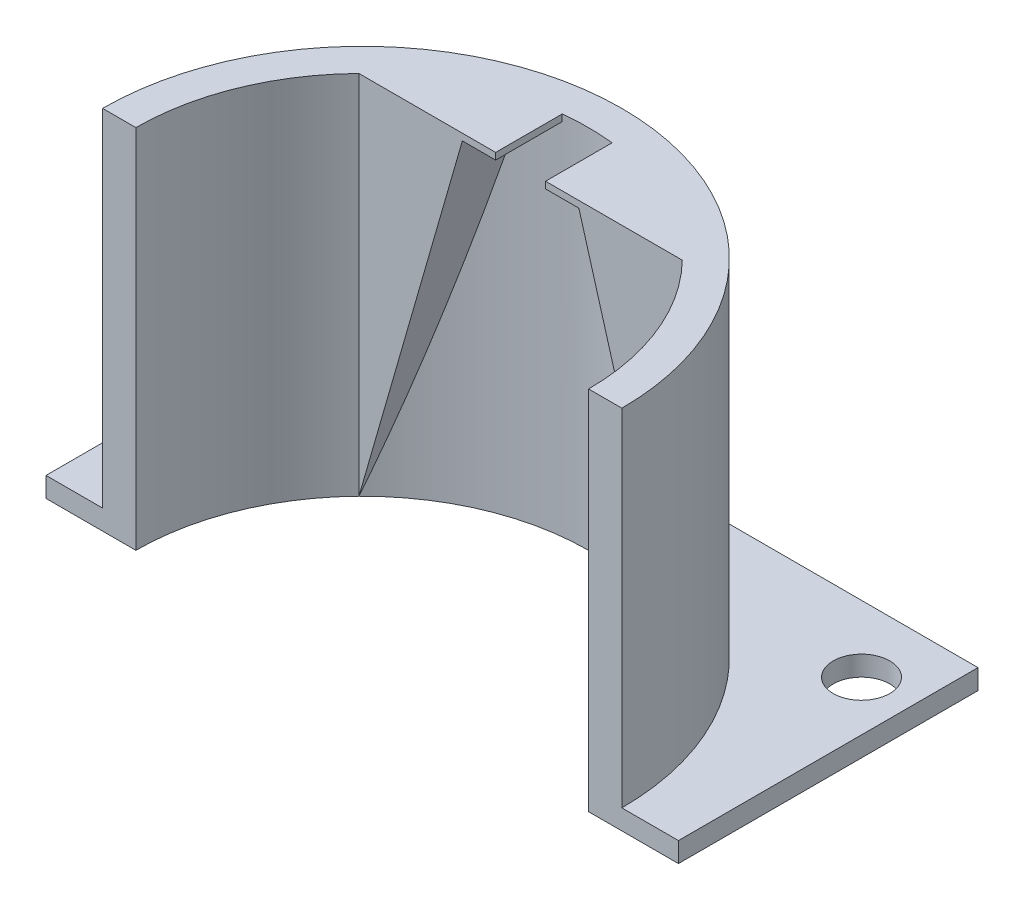
SolidWorks part; units mm, degrees
ref_plane "Front Plane" through (0, 0, 0) normal (0, 0, 1) x (1, 0, 0)
ref_plane "Top Plane" through (0, 0, 0) normal (0, 1, 0) x (1, 0, 0)
ref_plane "Right Plane" through (0, 0, 0) normal (1, 0, 0) x (0, 0, -1)
sketch "Sketch1" plane through (0, 0, 0) normal (0, 1, 0) x (1, 0, 0)
  line L0 (-47.5, 0) -> (47.5, 0)
  line L2 (-55, 0) -> (55, 0) construction
  line L3 (0, 0) -> (0, -45) construction
  line L4 (0, -55) -> (0, 55) construction
  line L5 (-47.5, 0) -> (-47.5, -45)
  line L7 (47.5, -45) -> (47.5, 0)
  line L8 (-47.5, -45) -> (-34, -45)
  line L9 (34, -45) -> (47.5, -45)
  arc A0 (34, -45) -> (-34, -45) centre (0, -45) ccw
  point P4 (0, 0)
  point P17 (0, -11)
  dimension "D3" = 68
  dimension "D4" = 34
  dimension "D1" = 95
  dimension "D2" = 45
extrude "Boss-Extrude1" add sketch "Sketch1" along normal blind 55
sketch "Sketch2" plane through (0, 55, 0) normal (0, 1, 0) x (1, 0, 0)
  line L0 (-47.5, -45) -> (-34, -45) construction
  line L1 (34, -45) -> (47.5, -45) construction
  line L2 (-39, -45) -> (-47.5, -45)
  line L3 (-47.5, -45) -> (-47.5, 0)
  line L4 (-47.5, 0) -> (47.5, 0)
  line L5 (47.5, 0) -> (47.5, -45)
  line L6 (47.5, -45) -> (39, -45)
  arc A0 (-39, -45) -> (39, -45) centre (0, -45) cw
  dimension "D1" = 39
extrude "Cut-Extrude1" cut sketch "Sketch2" against normal blind 52
sketch "Sketch3" plane through (0, 3, 0) normal (0, 1, 0) x (1, 0, 0)
  line L0 (47.5, 0) -> (-47.5, 0) construction
  line L1 (-40, -10) -> (-47.5, -10) construction
  line L2 (-47.5, 0) -> (-47.5, -45) construction
  line L3 (40, -10) -> (47.5, -10) construction
  line L4 (47.5, -45) -> (47.5, 0) construction
  circle A0 centre (-40, -10) radius 4.25
  circle A1 centre (40, -10) radius 4.25
  dimension "D1" = 8.5
  dimension "D2" = 80
  dimension "D3" = 10
extrude "Cut-Extrude2" cut sketch "Sketch3" against normal blind 5
sketch "Sketch4" plane through (0, 55, 0) normal (0, 1, 0) x (1, 0, 0)
  line L0 (-24.2881, -21.2074) -> (-3.75, -21.2074)
  line L1 (-3.75, -21.2074) -> (-3.75, -11.2074)
  line L2 (3.75, -21.2074) -> (3.75, -11.2074)
  line L3 (0, -21.2236) -> (0, -11) construction
  line L4 (0, -16.1118) -> (3.75, -16.1118) construction
  line L5 (0, -16.1118) -> (-3.75, -16.1118) construction
  line L6 (3.75, -21.2074) -> (24.2881, -21.2074)
  arc A0 (34, -45) -> (-34, -45) centre (0, -45) ccw construction
  arc A1 (24.2881, -21.2074) -> (3.75, -11.2074) centre (0, -45) ccw
  arc A2 (-24.2881, -21.2074) -> (-3.75, -11.2074) centre (0, -45) cw
  dimension "D1" = 7.5
  dimension "D2" = 10
extrude "Boss-Extrude2" add sketch "Sketch4" against normal blind 55
sketch "Sketch5" plane through (0, 0, 21.2074) normal (0, 0, 1) x (1, 0, 0)
  line L0 (-3.75, 54) -> (-8.75, 54)
  line L1 (-3.75, 0) -> (-3.75, 55) construction
  line L2 (-8.75, 54) -> (-8.75, 0)
  line L3 (-24.2881, 0) -> (-3.75, 0) construction
  line L4 (-8.75, 0) -> (-3.75, 0)
  line L5 (-3.75, 0) -> (-3.75, 54)
  line L6 (-24.2881, 55) -> (-3.75, 55) construction
  line L7 (0, -24.75) -> (0, 24.75) construction
  line L8 (8.75, 0) -> (3.75, 0)
  line L9 (8.75, 54) -> (8.75, 0)
  line L10 (3.75, 54) -> (8.75, 54)
  line L11 (3.75, 0) -> (3.75, 54)
  dimension "D1" = 1
  dimension "D2" = 5
extrude "Cut-Extrude3" cut sketch "Sketch5" against normal up to surface (9.0622 mm away) up to face at (0, 27.5, 11.1037)
sketch "Sketch8" plane through (0, 0, 21.2074) normal (0, 0, 1) x (1, 0, 0)
  line L0 (-8.75, 54) -> (-24.2881, 0)
  line L1 (-24.2881, 0) -> (-8.75, 0)
  line L2 (-8.75, 0) -> (-8.75, 54)
  line L3 (0, -24.75) -> (0, 24.75) construction
  line L4 (24.2881, 0) -> (8.75, 0)
  line L5 (8.75, 54) -> (24.2881, 0)
  line L6 (8.75, 0) -> (8.75, 54)
extrude "Cut-Extrude4" cut sketch "Sketch8" against normal up to surface up to face at (0, 40.75, 11.4838)
